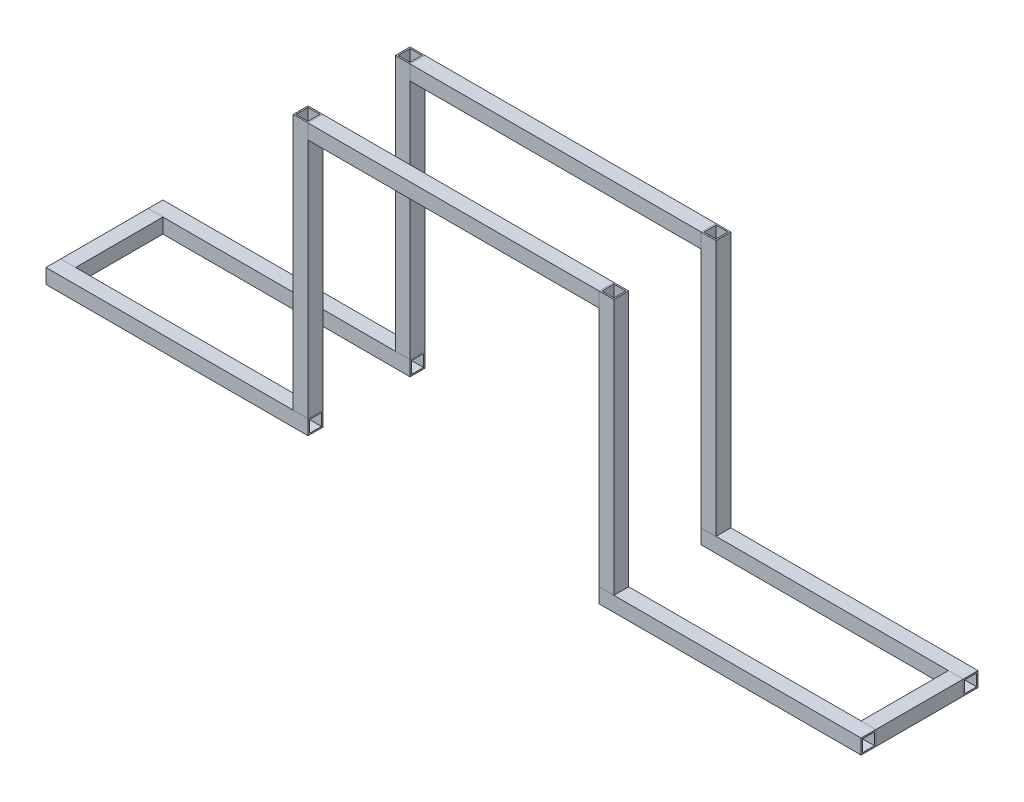
SolidWorks part; units mm, degrees
note: The reader was unsure of these and kept them because the rebuilt part matched: shared geometry of "Sketch3<3>", "Sketch3<4>".
ref_plane "Front Plane" through (0, 0, 0) normal (0, 0, 1) x (1, 0, 0)
ref_plane "Top Plane" through (0, 0, 0) normal (0, 1, 0) x (1, 0, 0)
ref_plane "Right Plane" through (0, 0, 0) normal (1, 0, 0) x (0, 0, -1)
sketch "Sketch3" plane through (0, 0, 0) normal (0, 0, 1) x (1, 0, 0)
  line L0 (-350, 0) -> (-125, 0)
  line L1 (-350, 12.7) -> (-125, 12.7)
  line L2 (-350, 0) -> (-350, 12.7)
  line L3 (350, 0) -> (350, 12.7)
  line L4 (-125, 144.73) -> (125, 144.73) construction
  line L9 (0, -55) -> (0, 55) construction
  line L10 (-125, 12.7) -> (-137.7, 12.7)
  line L11 (-125, 0) -> (-125, 232.7)
  line L12 (-125, 232.7) -> (-137.7, 232.7)
  line L13 (-137.7, 12.7) -> (-137.7, 232.7)
  line L14 (125, 232.7) -> (137.7, 232.7)
  line L15 (137.7, 12.7) -> (137.7, 232.7)
  line L16 (125, 12.7) -> (137.7, 12.7)
  line L17 (125, 0) -> (125, 232.7)
  line L18 (125, 12.7) -> (350, 12.7)
  line L19 (-350, 12.7) -> (350, 12.7) construction
  line L20 (125, 0) -> (350, 0)
  line L21 (-350, 0) -> (350, 0) construction
  line L22 (-337.3, 0) -> (-337.3, 12.7)
  line L23 (-137.7, 232.7) -> (137.7, 232.7)
  line L27 (125, 232.7) -> (-125, 232.7)
  line L28 (125, 232.7) -> (125, 220)
  line L29 (125, 220) -> (-125, 220)
  line L30 (-125, 232.7) -> (-125, 220)
  line L31 (337.3, 0) -> (337.3, 12.7)
  line L32 (0, 19.7) -> (-257.115, 326.1178) construction
  line L33 (0, 19.7) -> (-400, 19.7) construction
  line L35 (323.3, 358.5732) -> (28.16, 546.7018) construction
  point P11 (0, 144.73)
  point P31 (87.097, 19.7)
  dimension "D1" = 700
  dimension "D3" = 12.7
  dimension "D4" = 12.7
  dimension "D5" = 250
  dimension "D6" = 12.7
  dimension "D7" = 220
  dimension "D9" = 7
  dimension "D10" = 50
  dimension "D12" = 400
  dimension "D14" = 225
  dimension "D15" = 350
  dimension "D2" = 12.7
  dimension "D8" = 12.7
extrude "Boss-Extrude1" add sketch "Sketch3" along normal blind 12.7 contours L0 L11 L1 L2 | L17 L20 L3 L18 L16 | L29 L17 L23 L11 | L0 L22 L1 L2 | L31 L20 L3 L18
shell "Shell1" thickness 1.2
shell "Shell2" thickness 1.2
shell "Shell3" thickness 1.2
extrude "Boss-Extrude2" add sketch "Sketch3<3>" along normal blind 12.7 separate body contours L13 L1 L11 L12 | L17 L16 L15 L14
sketch "Sketch3<3>" plane through (0, 0, 0) normal (0, 0, 1) x (1, 0, 0) same geometry as "Sketch3"
shell "Shell4" thickness 1.2
shell "Shell5" thickness 1.2
extrude "Boss-Extrude3" add sketch "Sketch3<4>" against normal blind 75 separate body contours L0 L22 L1 L2 | L31 L20 L3 L18
sketch "Sketch3<4>" plane through (0, 0, 0) normal (0, 0, 1) x (1, 0, 0) same geometry as "Sketch3"
shell "Shell6" thickness 1.2
shell "Shell7" thickness 1.2
ref_plane "Plane1" through (0, 0, -37.5) normal (0, 0, 1) x (1, 0, 0)
mirror "Mirror1" about plane through (0, 0, -37.5) normal (0, 0, 1) of bodies 101 103 102 104 105
